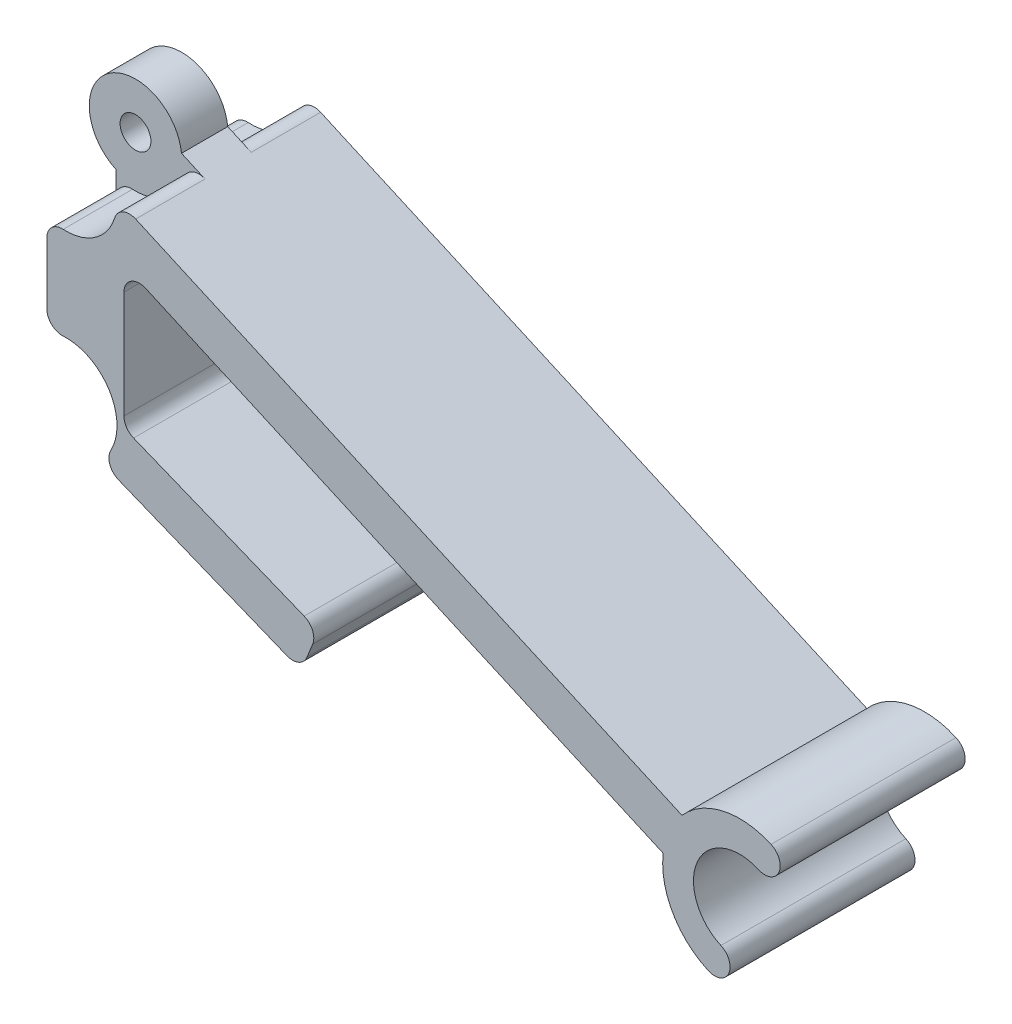
SolidWorks part; units mm, degrees
ref_plane "Front Plane" through (0, 0, 0) normal (0, 0, 1) x (1, 0, 0)
ref_plane "Top Plane" through (0, 0, 0) normal (0, 1, 0) x (1, 0, 0)
ref_plane "Right Plane" through (0, 0, 0) normal (1, 0, 0) x (0, 0, -1)
sketch "Sketch1" plane through (0, 0, 0) normal (0, 0, 1) x (1, 0, 0)
  line L0 (0.3327, 15.1693) -> (0.3327, 22.3049)
  line L2 (4.5662, 25.3457) -> (41.5395, 8.8842)
  line L3 (40.3192, 6.1435) -> (5.3327, 21.7206)
  line L7 (1.5827, 25.0321) -> (1.5827, 12.4421) construction
  line L9 (5.3327, 12.5448) -> (17.9531, 7.4459)
  line L11 (3.4297, 10.0781) -> (16.8292, 4.6643)
  line L12 (16.8292, 4.6643) -> (17.9531, 7.4459)
  line L13 (9.9681, 19.4037) -> (9.9681, 50019.4037) construction
  line L15 (0.3327, 18.7371) -> (2.3545, 18.7371) construction
  line L16 (17.3912, 6.0551) -> (1.5827, 12.4421) construction
  line L17 (45.2867, 5.5738) -> (1.5827, 25.0321) construction
  line L18 (46.9136, 9.228) -> (43.6597, 1.9197) construction
  line L20 (5.3327, 21.7206) -> (5.3327, 12.5448)
  arc A0 (0.3327, 22.3049) -> (4.5662, 25.3457) centre (1.5827, 25.0321) cw
  arc A1 (0.3327, 15.1693) -> (3.4297, 10.0781) centre (1.5827, 12.4421) ccw
  arc A2 (41.5395, 8.8842) -> (47.3204, 10.1416) centre (45.2867, 5.5738) cw
  arc A3 (47.3204, 10.1416) -> (46.5069, 8.3145) centre (46.9136, 9.228) cw
  arc A4 (46.5069, 8.3145) -> (44.0665, 2.8332) centre (45.2867, 5.5738) ccw
  arc A5 (44.0665, 2.8332) -> (43.253, 1.0061) centre (43.6597, 1.9197) cw
  arc A6 (43.253, 1.0061) -> (40.3192, 6.1435) centre (45.2867, 5.5738) cw
  circle A7 centre (1.5827, 25.0321) radius 1
  circle A8 centre (1.5827, 12.4421) radius 1
  dimension "D1" = 3
  dimension "D2" = 2
  dimension "D10" = 5
  dimension "D11" = 3
  dimension "D3" = 12.59
  dimension "D5" = 3
  dimension "D6" = 3
  dimension "D7" = 114
  dimension "D9" = 2.5
  dimension "D12" = 47.84
  dimension "D13" = 17.05
  dimension "D4" = 68
  dimension "D8" = 5
extrude "Boss-Extrude1" add sketch "Sketch1" along normal blind 12
ref_plane "midplane" through (0, 0, 6) normal (0, 0, 1) x (1, 0, 0)
sketch "Sketch2" plane through (0, 0, 12) normal (0, 0, 1) x (1, 0, 0)
  circle A0 centre (1.5827, 25.0321) radius 3.3
  circle A1 centre (1.5827, 12.4421) radius 3.3
  dimension "D1" = 6.6
extrude "Cut-Extrude1" cut sketch "Sketch2" against normal blind 4.5
mirror "Mirror1" about plane through (0, 0, 6) normal (0, 0, 1) of "Cut-Extrude1"
fillet "Fillet1" radius 1 4 edges at (0.3327, 15.4962, 2.25) (0.3327, 15.4962, 9.75) (0.3327, 21.978, 2.25) (0.3327, 21.978, 9.75)
fillet "Fillet2" radius 1 2 edges at (16.8292, 4.6643, 6) (17.9531, 7.4459, 6)
fillet "Fillet3" radius 1 2 edges at (5.3327, 21.7206, 6) (5.3327, 12.5448, 6)
fillet "Fillet6" radius 1 4 edges at (3.7461, 9.9502, 2.25) (3.7461, 9.9502, 9.75) (4.878, 25.2069, 2.25) (4.878, 25.2069, 9.75)
equation "\"axle-diameter\"=2"
equation "\"switch-thickness\"=12"
equation "\"base-width\"=4.0"
equation "\"axle-bushing-radius\"=3"
equation "\"D2@Sketch1\"=\"axle-diameter\""
equation "\"D1@Sketch1\"=\"axle-bushing-radius\""
equation "\"D1@Boss-Extrude1\"=\"switch-thickness\""
equation "\"D5@Sketch1\"=\"arm-width\""
equation "\"D6@Sketch1\"=\"arm-width\""
equation "\"D1@Sketch2\"=\"axle-bushing-radius\"*2.2"
equation "\"D1@Cut-Extrude1\"=\"switch-thickness\"/3+\"clearance\""
equation "\"clearance\"= 0.5"
equation "\"arm-width\"=3.0"
